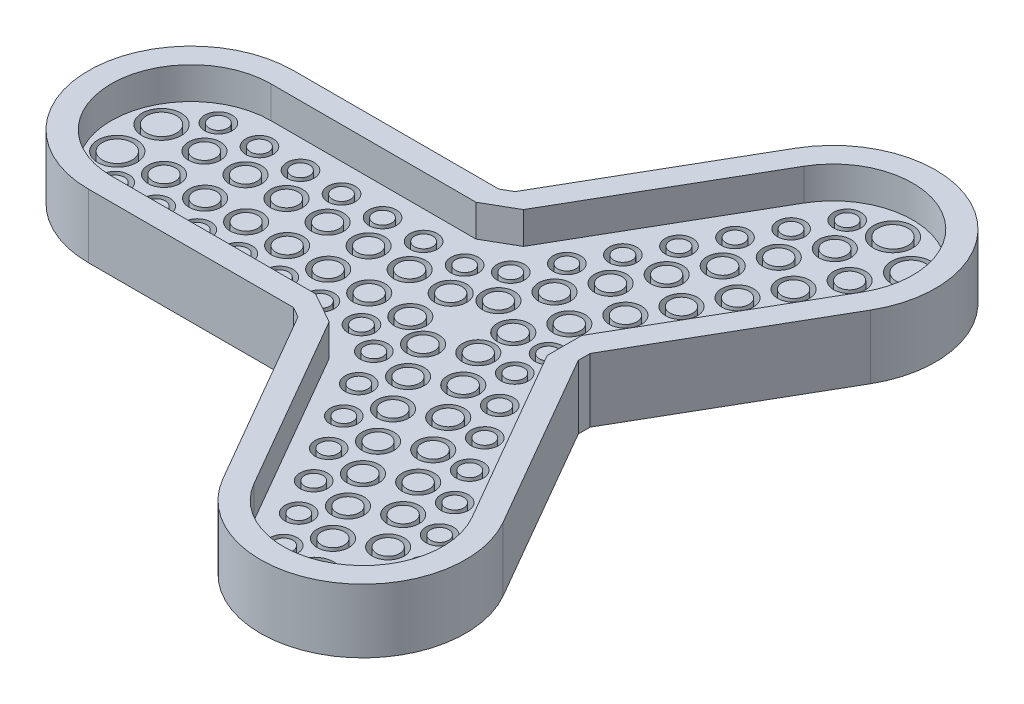
SolidWorks part; units mm, degrees
ref_plane "Front Plane" through (0, 0, 0) normal (0, 0, 1) x (1, 0, 0)
ref_plane "Top Plane" through (0, 0, 0) normal (0, 1, 0) x (1, 0, 0)
ref_plane "Right Plane" through (0, 0, 0) normal (1, 0, 0) x (0, 0, -1)
sketch "Sketch1" plane through (0, 0, 0) normal (0, 1, 0) x (1, 0, 0)
  line L0 (-22.5, 0) -> (22.5, 0) construction
  line L1 (-22.5, 17.5) -> (22.5, 17.5)
  line L2 (-22.5, -17.5) -> (22.5, -17.5)
  line L3 (-22.5, 22.5) -> (22.5, 22.5)
  line L4 (-22.5, -22.5) -> (22.5, -22.5)
  line L5 (86.2356, 40.2785) -> (63.7356, 1.3074)
  line L6 (47.2644, 62.7785) -> (24.7644, 23.8074)
  line L7 (66.75, 51.5285) -> (44.25, 12.5574) construction
  line L8 (81.9054, 42.7785) -> (59.4054, 3.8074)
  line L9 (51.5946, 60.2785) -> (29.0946, 21.3074)
  line L10 (47.2644, -62.7785) -> (24.7644, -23.8074)
  line L11 (86.2356, -40.2785) -> (63.7356, -1.3074)
  line L12 (66.75, -51.5285) -> (44.25, -12.5574) construction
  line L13 (51.5946, -60.2785) -> (29.0946, -21.3074)
  line L14 (81.9054, -42.7785) -> (59.4054, -3.8074)
  line L15 (59.4054, 3.8074) -> (59.4054, -3.8074)
  line L16 (63.7356, 1.3074) -> (63.7356, -1.3074)
  line L17 (22.5, 22.5) -> (24.7644, 23.8074)
  line L18 (22.5, 17.5) -> (29.0946, 21.3074)
  line L19 (22.2996, -17.5) -> (29.0946, -21.3074)
  line L20 (22.5, -22.5) -> (24.7644, -23.8074)
  arc A0 (-22.5, 17.5) -> (-22.5, -17.5) centre (-22.5, 0) ccw
  arc A2 (22.5, -22.5) -> (29.1948, -21.4809) centre (22.5, 0) ccw
  arc A3 (-22.5, 22.5) -> (-22.5, -22.5) centre (-22.5, 0) ccw
  arc A4 (24.7644, 23.8074) -> (22.2996, 17.5) centre (44.25, 12.5574) ccw
  arc A5 (86.2356, 40.2785) -> (47.2644, 62.7785) centre (66.75, 51.5285) ccw
  arc A6 (81.9054, 42.7785) -> (51.5946, 60.2785) centre (66.75, 51.5285) ccw
  arc A8 (63.7356, -1.3074) -> (59.5056, 3.9809) centre (44.25, -12.5574) ccw
  arc A9 (47.2644, -62.7785) -> (86.2356, -40.2785) centre (66.75, -51.5285) ccw
  arc A10 (51.5946, -60.2785) -> (81.9054, -42.7785) centre (66.75, -51.5285) ccw
  arc A13 (22.5, -17.5) -> (22.5, 17.5) centre (22.5, 0) ccw construction
  arc A14 (29.1948, 21.4809) -> (22.5, 22.5) centre (22.5, 0) ccw
  arc A15 (22.5, -22.5) -> (22.5, 22.5) centre (22.5, 0) ccw construction
  arc A16 (22.2996, -17.5) -> (24.7644, -23.8074) centre (44.25, -12.5574) ccw
  arc A19 (59.5056, -3.9809) -> (63.7356, 1.3074) centre (44.25, 12.5574) ccw
  point P2 (0, 0)
  point P20 (55.5, 32.0429)
  point P33 (55.5, -32.0429)
  point P44 (37, 0)
  dimension "D1" = 37
  dimension "D2" = 35
  dimension "D4" = 3
  dimension "D3" = 5
extrude "Boss-Extrude1" add sketch "Sketch1" along normal blind 14 contours A16 L2 A0 L1 A4 A14 L3 A3 L4 A2 | L19 A16 A2 L13 | A19 L14 A10 L13 A2 A16 L10 A9 L11 A8 | A16 A2 L20 | A8 A19 L5 A5 L6 A4 A14 L9 A6 L8 | L9 A14 A4 L1 L18 | A14 A4 L17 | L14 A19 A8 L8 L15 | A19 A8 L16 region at (-40.8241, 0, 0) region at (25.1868, 0, -20.4611) region at (23.7665, 0, -22.9212) region at (25.2614, 0, -22.6698) region at (25.2008, 0, 20.504) region at (23.7665, 0, 22.9212) region at (26.8274, 0, 23.0844) region at (63.4671, 0, 0) region at (60.6265, 0, 0)
extrude "Boss-Extrude2" add sketch "Sketch1<2>" along normal blind 7 contours L2 L1 A0 region at (36.9993, 0, 0.001)
sketch "Sketch1<2>" plane through (0, 0, 0) normal (0, 1, 0) x (1, 0, 0) same geometry as "Sketch1"
sketch "Sketch2" plane through (0, 7, 0) normal (0, 1, 0) x (1, 0, 0)
  line L2 (-1000, 0) -> (49000, 0) construction
  line L4 (-22.5, -17.5) -> (22.2996, -17.5)
  line L14 (-22.5, -17.5) -> (22.2996, -17.5)
  line L16 (22.5, 17.5) -> (-22.5, 17.5)
  line L18 (22.5, 17.5) -> (-22.5, 17.5)
  line L20 (29.0946, -21.3074) -> (51.5946, -60.2785)
  line L22 (29.0946, -21.3074) -> (51.5946, -60.2785)
  line L24 (81.9054, -42.7785) -> (59.4054, -3.8074)
  line L26 (81.9054, -42.7785) -> (59.4054, -3.8074)
  line L28 (59.4054, -3.8074) -> (59.4054, 3.8074)
  line L30 (59.4054, -3.8074) -> (59.4054, 3.8074)
  line L31 (59.4054, 3.8074) -> (81.9054, 42.7785)
  line L32 (59.4054, 3.8074) -> (81.9054, 42.7785)
  line L33 (51.5946, 60.2785) -> (29.0946, 21.3074)
  line L34 (51.5946, 60.2785) -> (29.0946, 21.3074)
  line L35 (29.0946, 21.3074) -> (22.5, 17.5)
  line L36 (29.0946, 21.3074) -> (22.5, 17.5)
  line L37 (22.2996, -17.5) -> (29.0946, -21.3074)
  line L38 (22.2996, -17.5) -> (29.0946, -21.3074)
  circle A2 centre (-23.9882, 4.4317) radius 2.5
  circle A3 centre (-14.9882, 4.4317) radius 2.5
  arc A4 (-22.5, 17.5) -> (-22.5, -17.5) centre (-22.5, 0) ccw
  circle A8 centre (-5.9882, 4.4317) radius 2.5
  circle A9 centre (3.0118, 4.4317) radius 2.5
  circle A10 centre (12.0118, 4.4317) radius 2.5
  circle A11 centre (21.0118, 4.4317) radius 2.5
  circle A12 centre (30.0118, 4.4317) radius 2.5
  circle A27 centre (30.0118, -4.4317) radius 2.5
  circle A28 centre (21.0118, -4.4317) radius 2.5
  circle A29 centre (12.0118, -4.4317) radius 2.5
  circle A30 centre (3.0118, -4.4317) radius 2.5
  circle A31 centre (-5.9882, -4.4317) radius 2.5
  circle A32 centre (-14.9882, -4.4317) radius 2.5
  circle A33 centre (-23.9882, -4.4317) radius 2.5
  circle A34 centre (-27.8096, -11.315) radius 2
  circle A35 centre (-18.8096, -11.315) radius 2
  circle A36 centre (-9.8096, -11.315) radius 2
  circle A37 centre (-0.8096, -11.315) radius 2
  circle A38 centre (8.1904, -11.315) radius 2
  circle A39 centre (17.1904, -11.315) radius 2
  circle A40 centre (26.1904, -11.315) radius 2
  circle A53 centre (26.1904, 11.315) radius 2
  circle A54 centre (17.1904, 11.315) radius 2
  circle A55 centre (8.1904, 11.315) radius 2
  circle A56 centre (-0.8096, 11.315) radius 2
  circle A57 centre (-9.8096, 11.315) radius 2
  circle A58 centre (-18.8096, 11.315) radius 2
  circle A59 centre (-27.8096, 11.315) radius 2
  circle A64 centre (30.0118, -4.4317) radius 3.5
  circle A65 centre (21.0118, -4.4317) radius 3.5
  circle A66 centre (12.0118, -4.4317) radius 3.5
  circle A67 centre (3.0118, -4.4317) radius 3.5
  circle A68 centre (-5.9882, -4.4317) radius 3.5
  circle A69 centre (-14.9882, -4.4317) radius 3.5
  circle A70 centre (-27.8096, -11.315) radius 3
  circle A71 centre (-18.8096, -11.315) radius 3
  circle A72 centre (-9.8096, -11.315) radius 3
  circle A73 centre (-0.8096, -11.315) radius 3
  circle A74 centre (8.1904, -11.315) radius 3
  circle A75 centre (17.1904, -11.315) radius 3
  circle A76 centre (26.1904, -11.315) radius 3
  circle A81 centre (-23.9882, -4.4317) radius 3.5
  circle A83 centre (-23.9882, 4.4317) radius 3.5
  circle A84 centre (-14.9882, 4.4317) radius 3.5
  circle A85 centre (-5.9882, 4.4317) radius 3.5
  circle A86 centre (3.0118, 4.4317) radius 3.5
  circle A87 centre (12.0118, 4.4317) radius 3.5
  circle A88 centre (21.0118, 4.4317) radius 3.5
  circle A89 centre (30.0118, 4.4317) radius 3.5
  circle A97 centre (26.1904, 11.315) radius 3
  circle A98 centre (17.1904, 11.315) radius 3
  circle A99 centre (8.1904, 11.315) radius 3
  circle A100 centre (-0.8096, 11.315) radius 3
  circle A101 centre (-9.8096, 11.315) radius 3
  circle A102 centre (-18.8096, 11.315) radius 3
  circle A103 centre (-27.8096, 11.315) radius 3
  circle A105 centre (-33.7648, 4.7998) radius 3.2873
  circle A106 centre (-33.5196, -5.1591) radius 3.2873
  circle A107 centre (-33.5196, -5.1591) radius 4.2873
  circle A108 centre (-33.7648, 4.7998) radius 4.2873
  circle A109 centre (71.3321, 50.6015) radius 2.5
  circle A110 centre (66.8321, 42.8072) radius 2.5
  circle A111 centre (62.3321, 35.013) radius 2.5
  arc A112 (-22.5, 17.5) -> (-22.5, -17.5) centre (-22.5, 0) ccw
  arc A114 (51.5946, -60.2785) -> (81.9054, -42.7785) centre (66.75, -51.5285) ccw
  circle A116 centre (57.8321, 27.2188) radius 2.5
  circle A117 centre (53.3321, 19.4246) radius 2.5
  circle A118 centre (48.8321, 11.6303) radius 2.5
  circle A119 centre (44.3321, 3.8361) radius 2.5
  circle A120 centre (36.6561, 8.2678) radius 2.5
  circle A121 centre (41.1561, 16.0621) radius 2.5
  circle A122 centre (45.6561, 23.8563) radius 2.5
  circle A123 centre (50.1561, 31.6505) radius 2.5
  circle A124 centre (54.6561, 39.4447) radius 2.5
  circle A125 centre (59.1561, 47.239) radius 2.5
  circle A126 centre (63.6561, 55.0332) radius 2.5
  circle A127 centre (59.6057, 61.7843) radius 2
  circle A128 centre (55.1057, 53.99) radius 2
  circle A129 centre (50.6057, 46.1958) radius 2
  circle A130 centre (46.1057, 38.4016) radius 2
  circle A131 centre (41.6057, 30.6074) radius 2
  circle A132 centre (37.1057, 22.8131) radius 2
  circle A133 centre (32.6057, 15.0189) radius 2
  circle A134 centre (52.2039, 3.7039) radius 2
  circle A135 centre (56.7039, 11.4981) radius 2
  circle A136 centre (61.2039, 19.2923) radius 2
  circle A137 centre (65.7039, 27.0866) radius 2
  circle A138 centre (70.2039, 34.8808) radius 2
  circle A139 centre (74.7039, 42.675) radius 2
  circle A140 centre (79.2039, 50.4693) radius 2
  circle A141 centre (36.6561, 8.2678) radius 3.5
  circle A142 centre (41.1561, 16.0621) radius 3.5
  circle A143 centre (45.6561, 23.8563) radius 3.5
  circle A144 centre (50.1561, 31.6505) radius 3.5
  circle A145 centre (54.6561, 39.4447) radius 3.5
  circle A146 centre (59.1561, 47.239) radius 3.5
  circle A147 centre (59.6057, 61.7843) radius 3
  circle A148 centre (55.1057, 53.99) radius 3
  circle A149 centre (50.6057, 46.1958) radius 3
  circle A150 centre (46.1057, 38.4016) radius 3
  circle A151 centre (41.6057, 30.6074) radius 3
  circle A152 centre (37.1057, 22.8131) radius 3
  circle A153 centre (32.6057, 15.0189) radius 3
  circle A154 centre (63.6561, 55.0332) radius 3.5
  circle A155 centre (71.3321, 50.6015) radius 3.5
  circle A156 centre (66.8321, 42.8072) radius 3.5
  circle A157 centre (62.3321, 35.013) radius 3.5
  circle A158 centre (57.8321, 27.2188) radius 3.5
  circle A159 centre (53.3321, 19.4246) radius 3.5
  circle A160 centre (48.8321, 11.6303) radius 3.5
  circle A161 centre (44.3321, 3.8361) radius 3.5
  circle A162 centre (52.2039, 3.7039) radius 3
  circle A163 centre (56.7039, 11.4981) radius 3
  circle A164 centre (61.2039, 19.2923) radius 3
  circle A165 centre (65.7039, 27.0866) radius 3
  circle A166 centre (70.2039, 34.8808) radius 3
  circle A167 centre (74.7039, 42.675) radius 3
  circle A168 centre (79.2039, 50.4693) radius 3
  circle A169 centre (76.5392, 58.8842) radius 3.2873
  circle A170 centre (67.7919, 63.6512) radius 3.2873
  circle A171 centre (67.7919, 63.6512) radius 4.2873
  circle A172 centre (76.5392, 58.8842) radius 4.2873
  arc A173 (81.9054, 42.7785) -> (51.5946, 60.2785) centre (66.75, 51.5285) ccw
  circle A174 centre (63.6561, -55.0332) radius 2.5
  circle A175 centre (59.1561, -47.239) radius 2.5
  circle A176 centre (54.6561, -39.4447) radius 2.5
  circle A177 centre (50.1561, -31.6505) radius 2.5
  circle A178 centre (45.6561, -23.8563) radius 2.5
  circle A179 centre (41.1561, -16.0621) radius 2.5
  circle A180 centre (36.6561, -8.2678) radius 2.5
  circle A181 centre (44.3321, -3.8361) radius 2.5
  circle A182 centre (48.8321, -11.6303) radius 2.5
  circle A183 centre (53.3321, -19.4246) radius 2.5
  circle A184 centre (57.8321, -27.2188) radius 2.5
  circle A185 centre (62.3321, -35.013) radius 2.5
  circle A186 centre (66.8321, -42.8072) radius 2.5
  circle A187 centre (71.3321, -50.6015) radius 2.5
  circle A188 centre (79.2039, -50.4693) radius 2
  circle A189 centre (74.7039, -42.675) radius 2
  circle A190 centre (70.2039, -34.8808) radius 2
  circle A191 centre (65.7039, -27.0866) radius 2
  circle A192 centre (61.2039, -19.2923) radius 2
  circle A193 centre (56.7039, -11.4981) radius 2
  circle A194 centre (52.2039, -3.7039) radius 2
  circle A195 centre (32.6057, -15.0189) radius 2
  circle A196 centre (37.1057, -22.8131) radius 2
  circle A197 centre (41.6057, -30.6074) radius 2
  circle A198 centre (46.1057, -38.4016) radius 2
  circle A199 centre (50.6057, -46.1958) radius 2
  circle A200 centre (55.1057, -53.99) radius 2
  circle A201 centre (59.6057, -61.7843) radius 2
  circle A202 centre (44.3321, -3.8361) radius 3.5
  circle A203 centre (48.8321, -11.6303) radius 3.5
  circle A204 centre (53.3321, -19.4246) radius 3.5
  circle A205 centre (57.8321, -27.2188) radius 3.5
  circle A206 centre (62.3321, -35.013) radius 3.5
  circle A207 centre (66.8321, -42.8072) radius 3.5
  circle A208 centre (79.2039, -50.4693) radius 3
  circle A209 centre (74.7039, -42.675) radius 3
  circle A210 centre (70.2039, -34.8808) radius 3
  circle A211 centre (65.7039, -27.0866) radius 3
  circle A212 centre (61.2039, -19.2923) radius 3
  circle A213 centre (56.7039, -11.4981) radius 3
  circle A214 centre (52.2039, -3.7039) radius 3
  circle A215 centre (71.3321, -50.6015) radius 3.5
  circle A216 centre (63.6561, -55.0332) radius 3.5
  circle A217 centre (59.1561, -47.239) radius 3.5
  circle A218 centre (54.6561, -39.4447) radius 3.5
  circle A219 centre (50.1561, -31.6505) radius 3.5
  circle A220 centre (45.6561, -23.8563) radius 3.5
  circle A221 centre (41.1561, -16.0621) radius 3.5
  circle A222 centre (36.6561, -8.2678) radius 3.5
  circle A223 centre (32.6057, -15.0189) radius 3
  circle A224 centre (37.1057, -22.8131) radius 3
  circle A225 centre (41.6057, -30.6074) radius 3
  circle A226 centre (46.1057, -38.4016) radius 3
  circle A227 centre (50.6057, -46.1958) radius 3
  circle A228 centre (55.1057, -53.99) radius 3
  circle A229 centre (59.6057, -61.7843) radius 3
  circle A230 centre (68.2256, -63.6841) radius 3.2873
  circle A231 centre (76.7276, -58.4922) radius 3.2873
  circle A232 centre (76.7276, -58.4922) radius 4.2873
  circle A233 centre (68.2256, -63.6841) radius 4.2873
  arc A234 (51.5946, -60.2785) -> (81.9054, -42.7785) centre (66.75, -51.5285) ccw
  arc A238 (51.5946, -60.2785) -> (81.9054, -42.7785) centre (66.75, -51.5285) ccw
  arc A239 (81.9054, 42.7785) -> (51.5946, 60.2785) centre (66.75, 51.5285) ccw
  arc A240 (81.9054, 42.7785) -> (51.5946, 60.2785) centre (66.75, 51.5285) ccw
  point P380 (37, 0)
  dimension "D7" = 5
  dimension "D8" = 4
  dimension "D9" = 1
  dimension "D4" = 6
  dimension "D5" = 9
  dimension "D10" = 3
  dimension "D1" = 0
  dimension "D6" = 1
  dimension "D2" = 7
  dimension "D3" = 7
extrude "Cut-Extrude1" cut sketch "Sketch2" against normal blind 4 contours A107 A106 | A108 A105 | A83 A2 | A81 A33 | A69 A32 | A71 A35 | A70 A34 | A72 A36 | A84 A3 | A103 A59 | A102 A58 | A101 A57 | A100 A56 | A85 A8 | A86 A9 | A68 A31 | A67 A30 | A73 A37 | A74 A38 | A66 A29 | A87 A10 | A99 A55 | A98 A54 | A97 A53 | A89 A12 | A88 A11 | A65 A28 | A64 A27 | A76 A40 | A75 A39 | A223 A195 | A222 A180 | A221 A179 | A224 A196 | A220 A178 | A225 A197 | A204 A183 | A203 A182 | A219 A177 | A226 A198 | A227 A199 | A218 A176 | A206 A185 | A207 A186 | A210 A190 | A209 A189 | A217 A175 | A228 A200 | A215 A187 | A216 A174 | A208 A188 | A232 A231 | A233 A230 | A229 A201 | A211 A191 | A205 A184 | A212 A192 | A202 A181 | A214 A194 | A161 A119 | A162 A134 | A141 A120 | A153 A133 | A142 A121 | A160 A118 | A163 A135 | A159 A117 | A152 A132 | A143 A122 | A151 A131 | A150 A130 | A144 A123 | A145 A124 | A157 A111 | A158 A116 | A165 A137 | A166 A138 | A149 A129 | A146 A125 | A156 A110 | A147 A127 | A148 A128 | A154 A126 | A171 A170 | A172 A169 | A168 A140 | A167 A139 | A155 A109 | A164 A136 | A213 A193 region at (26.6108, 7, 4.4317) region at (17.6108, 7, 4.4317) region at (8.6108, 7, 4.4317) region at (-0.3892, 7, 4.4317) region at (-9.3892, 7, 4.4317) region at (-18.3892, 7, 4.4317) region at (-30.7248, 7, 11.315) region at (-21.7248, 7, 11.315) region at (-12.7248, 7, 11.315) region at (-3.7248, 7, 11.315) region at (5.2752, 7, 11.315) region at (14.2752, 7, 11.315) region at (23.2752, 7, 11.315) region at (-27.3892, 7, 4.4317) region at (-27.3892, 7, -4.4317) region at (-18.3892, 7, -4.4317) region at (-9.3892, 7, -4.4317) region at (-0.3892, 7, -4.4317) region at (8.6108, 7, -4.4317) region at (17.6108, 7, -4.4317) region at (26.6108, 7, -4.4317) region at (23.2752, 7, -11.315) region at (14.2752, 7, -11.315) region at (5.2752, 7, -11.315) region at (-3.7248, 7, -11.315) region at (-12.7248, 7, -11.315) region at (-21.7248, 7, -11.315) region at (-30.7248, 7, -11.315) region at (-37.6856, 7, 5.1591) region at (-37.9309, 7, -4.7998) region at (33.2551, 7, -8.2678) region at (37.7551, 7, -16.0621) region at (42.2551, 7, -23.8563) region at (46.7551, 7, -31.6505) region at (51.2551, 7, -39.4447) region at (55.7551, 7, -47.239) region at (56.6906, 7, -61.7843) region at (52.1906, 7, -53.99) region at (47.6906, 7, -46.1958) region at (43.1906, 7, -38.4016) region at (38.6906, 7, -30.6074) region at (34.1906, 7, -22.8131) region at (29.6906, 7, -15.0189) region at (60.2551, 7, -55.0332) region at (67.9311, 7, -50.6015) region at (63.4311, 7, -42.8072) region at (58.9311, 7, -35.013) region at (54.4311, 7, -27.2188) region at (49.9311, 7, -19.4246) region at (45.4311, 7, -11.6303) region at (40.9311, 7, -3.8361) region at (49.2887, 7, -3.7039) region at (53.7887, 7, -11.4981) region at (58.2887, 7, -19.2923) region at (62.7887, 7, -27.0866) region at (67.2887, 7, -34.8808) region at (71.7887, 7, -42.675) region at (76.2887, 7, -50.4693) region at (63.6259, 7, -63.6512) region at (72.3732, 7, -58.8842)
